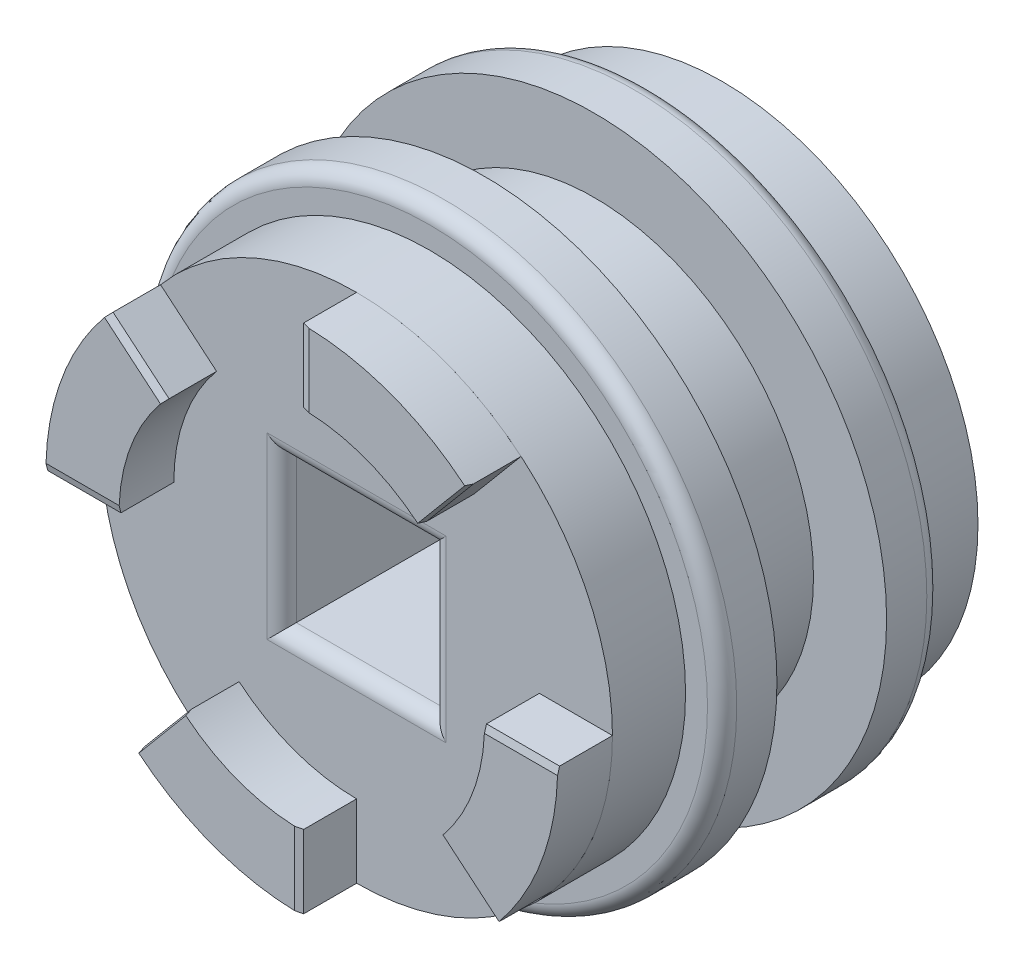
SolidWorks part; units mm, degrees
note: '?' marks a value the reader was unsure of. The reader was unsure of these and kept them because the rebuilt part matched: shared geometry of "Sketch12<2>", "Sketch11<3>".
ref_plane "Front Plane" through (0, 0, 0) normal (0, 0, 1) x (1, 0, 0)
ref_plane "Top Plane" through (0, 0, 0) normal (0, 1, 0) x (1, 0, 0)
ref_plane "Right Plane" through (0, 0, 0) normal (1, 0, 0) x (0, 0, -1)
sketch "Sketch1" plane through (0, 0, 0) normal (0, 0, 1) x (1, 0, 0)
  circle A0 centre (0, 0) radius 7
  dimension "D1" = 14
extrude "Boss-Extrude1" add sketch "Sketch1" along normal blind 10
sketch "Sketch2" plane through (0, 0, 10) normal (0, 0, 1) x (1, 0, 0)
  line L0 (0, 5) -> (0, 7)
  line L1 (3.2139, 3.8302) -> (4.4995, 5.3623)
  line L2 (0.6959, 4.9513) -> (0.9742, 6.9319)
  arc A0 (0, 7) -> (4.4995, 5.3623) centre (0, 0) cw
  circle A1 centre (0, 0) radius 7 construction
  arc A2 (0, 5) -> (3.2139, 3.8302) centre (0, 0) cw
  circle M5 centre (0, 0) radius 7
  dimension "D1" = 5
  dimension "D3" = 8
  dimension "D2" = 40
extrude "Boss-Extrude2" add sketch "Sketch2" along normal blind 1.5 separate body contours L0 A2 L2 M5 | L2 A2 L1 M5
ref_axis "Axis1" through (0, 0, 10) along (0, 0, -1)?
ref_plane "Plane1" through (0, 7, 0) normal (0, 1, 0) x (1, 0, 0)
sketch "Sketch10" plane through (0, 7, 0) normal (0, 1, 0) x (1, 0, 0)
  line L0 (0, -10) -> (4.4995, -10)
  line L1 (4.4995, -10) -> (4.4995, -11.5)
  line L2 (4.4995, -11.5) -> (3.2139, -11.5)
  line L3 (0, -10.7) -> (0, -10)
  line L4 (0, -10.7) -> (3.2139, -11.5)
  line L5 (4.4995, -10) -> (0, -10) construction
  dimension "D1" = 0.8
wrap "Wrap1" [suppressed] sketch "Sketch10" source sketch "Sketch10" thickness 3 parameters "D1"=3
chamfer "Chamfer2" distance 0.2 angle 15 2 edges at (3.8567, 4.5963, 11.5) (0, 6, 11.5)
fillet "Fillet1" [suppressed] radius 0.2
pattern_circular "CirPattern1" count 4 over 360 about axis through (0, 0, 0) along (0, 0, 1) of bodies 102
sketch "Sketch11" plane through (0, 0, 0) normal (0, 0, -1) x (-1, 0, 0)
  line L1 (2.05, -2.05) -> (-2.05, -2.05)
  line L2 (2.05, -2.05) -> (2.05, 2.05)
  line L3 (2.05, 2.05) -> (-2.05, 2.05)
  line L4 (-2.05, -2.05) -> (-2.05, 2.05)
  line L5 (2.05, -2.05) -> (-2.05, 2.05) construction
  line L6 (2.05, 2.05) -> (-2.05, -2.05) construction
  circle A0 centre (0, 0) radius 4
  point P0 (0, 0)
  dimension "D2" = 8
  dimension "D1" = 4.1
extrude "Cut-Extrude1" cut sketch "Sketch11" against normal up to next (10 mm away) contours L4 L1 L2 L3
ref_plane "Plane2" through (0, 0, 5) normal (0, 0, 1) x (1, 0, 0)
sketch "Sketch12" plane through (0, 0, 5) normal (0, 0, 1) x (1, 0, 0)
  circle A0 centre (0, 0) radius 8
  circle A1 centre (0, 0) radius 7
  dimension "D1" = 16
  dimension "D2" = 14
extrude "Boss-Extrude3" add sketch "Sketch12" along normal mid plane 6
extrude "Cut-Extrude-Thin1" cut sketch "Sketch12<2>" against normal mid plane 3 thin contours A0
sketch "Sketch12<2>" plane through (0, 0, 5) normal (0, 0, 1) x (1, 0, 0) same geometry as "Sketch12"
fillet "Fillet3" radius 0.4 2 edges at (8, 0, 2) (8, 0, 8)
extrude "Cut-Extrude2" cut sketch "Sketch11<3>" against normal blind 2 contours A0 L1 L4 L3 L2
sketch "Sketch11<3>" plane through (0, 0, 0) normal (0, 0, -1) x (-1, 0, 0) same geometry as "Sketch11"
fillet "Fillet2" radius 0.4 8 edges at (-2.05, 0, 2) (0, -2.05, 2) (2.05, 0, 2) (0, 2.05, 2) (2.05, 0, 10) (0, 2.05, 10) (-2.05, 0, 10) (0, -2.05, 10)
